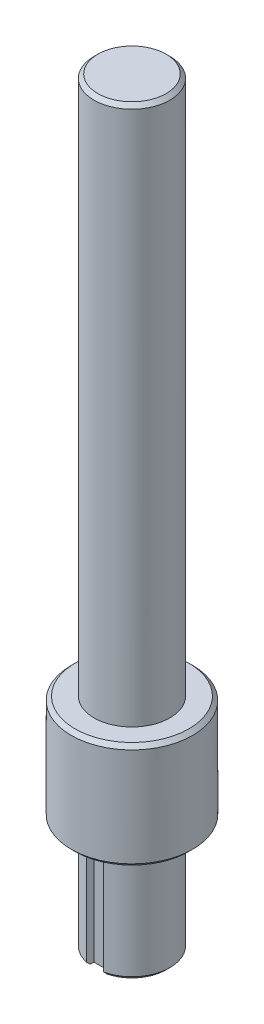
SolidWorks part; units mm, degrees
ref_plane "Front Plane" through (0, 0, 0) normal (0, 0, 1) x (1, 0, 0)
ref_plane "Top Plane" through (0, 0, 0) normal (0, 1, 0) x (1, 0, 0)
ref_plane "Right Plane" through (0, 0, 0) normal (1, 0, 0) x (0, 0, -1)
sketch "Sketch1" plane through (0, 0, 0) normal (0, 0, 1) x (1, 0, 0)
  line L0 (0, 0) -> (5, 0)
  line L3 (5, 29) -> (5, 100)
  line L4 (5, 100) -> (0, 100)
  line L5 (0, 100) -> (0, 0)
  line L6 (5, 29) -> (8, 29)
  line L7 (8, 29) -> (8, 15)
  line L8 (8, 15) -> (5, 15)
  line L9 (5, 15) -> (5, 0)
  dimension "D1" = 5
  dimension "D2" = 5
  dimension "D3" = 14
  dimension "D4" = 8
  dimension "D5" = 15
  dimension "D6" = 100
revolve "Revolve1" add sketch "Sketch1" angle 360 about L5
sketch "Sketch2" plane through (0, 0, 0) normal (0, -1, 0) x (1, 0, 0)
  line L1 (-1.125, 6.125) -> (1.125, 6.125)
  line L2 (-1.125, 6.125) -> (-1.125, 3.875)
  line L3 (-1.125, 3.875) -> (1.125, 3.875)
  line L4 (1.125, 6.125) -> (1.125, 3.875)
  line L5 (-1.125, 6.125) -> (1.125, 3.875) construction
  line L6 (-1.125, 3.875) -> (1.125, 6.125) construction
  circle A0 centre (0, 0) radius 5 construction
  point P0 (0, 5)
  dimension "D1" = 2.25
extrude "Cut-Extrude1" cut sketch "Sketch2" against normal up to surface (15 mm away) up to face at (-8, 15, 0)
chamfer "Chamfer1" distance 0.5 angle 45 2 edges at (-8, 15, 0) (-8, 29, 0)
chamfer "Chamfer2" distance 0.5 angle 45 2 edges at (-5, 100, 0) (0, 0, -5)
ref_axis "Axis1" through (0, 29, 0) along (0, 1, 0)
